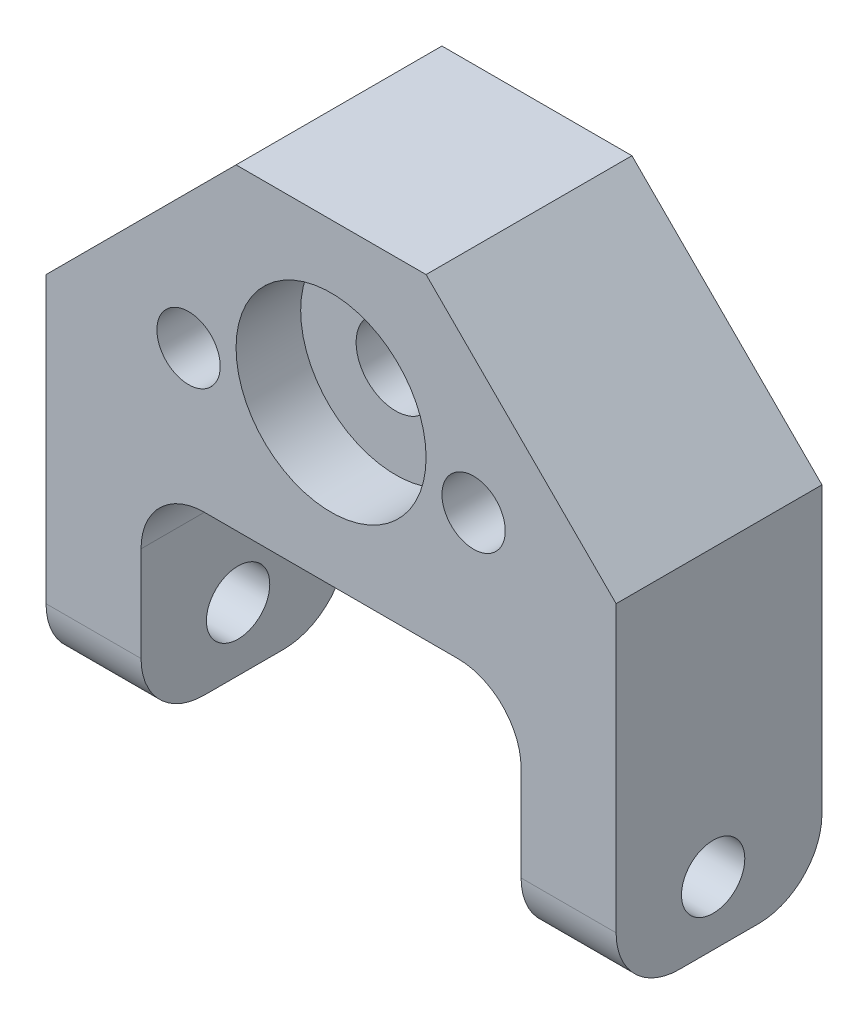
SolidWorks part; units mm, degrees
material "1060 Alloy"
ref_plane "Front" through (0, 0, 0) normal (0, 0, 1) x (1, 0, 0)
ref_plane "Top" through (0, 0, 0) normal (0, 1, 0) x (1, 0, 0)
ref_plane "Right" through (0, 0, 0) normal (1, 0, 0) x (0, 0, -1)
sketch "Sketch1" plane through (0, 0, 0) normal (0, 0, 1) x (1, 0, 0)
  line L1 (28.575, -15.875) -> (-28.575, -15.875)
  line L2 (28.575, -15.875) -> (28.575, 15.875)
  line L3 (28.575, 15.875) -> (-28.575, 15.875)
  line L4 (-28.575, -15.875) -> (-28.575, 15.875)
  line L5 (28.575, -15.875) -> (-28.575, 15.875) construction
  line L6 (28.575, 15.875) -> (-28.575, -15.875) construction
  point P0 (0, 0)
  dimension "D1" = 31.75
  dimension "D2" = 57.15
extrude "Boss-Extrude1" add sketch "Sketch1" along normal blind 20.6375
sketch "Sketch2" plane through (0, 0, 0) normal (0, 0, -1) x (-1, 0, 0)
  circle A0 centre (0, 0) radius 11.1125
  dimension "D1" = 22.225
extrude "Cut-Extrude1" cut sketch "Sketch2" against normal blind 6.985
sketch "Sketch3" plane through (0, 0, 6.985) normal (0, 0, -1) x (-1, 0, 0)
  circle A0 centre (0, 0) radius 8.255
  dimension "D1" = 16.51
extrude "Cut-Extrude2" cut sketch "Sketch3" against normal blind 2.413
sketch "Sketch4" plane through (0, 0, 9.398) normal (0, 0, -1) x (-1, 0, 0)
  circle A0 centre (0, 0) radius 3.9688
  dimension "D1" = 7.9375
extrude "Cut-Extrude3" cut sketch "Sketch4" against normal through all
sketch "Sketch6" plane through (0, 0, 9.398) normal (0, 0, -1) x (-1, 0, 0)
  circle A0 centre (0, 0) radius 9.525
  dimension "D1" = 19.05
extrude "Cut-Extrude4" cut sketch "Sketch6" against normal through all from offset 4.7625 offset against normal yes
sketch "Sketch7" plane through (0, -15.875, 0) normal (0, -1, 0) x (1, 0, 0)
  line L0 (-28.575, 0) -> (28.575, 0) construction
  line L1 (-28.575, 20.6375) -> (-19.05, 20.6375)
  line L2 (-28.575, 20.6375) -> (-28.575, 0)
  line L3 (-28.575, 0) -> (-19.05, 0)
  line L4 (-19.05, 20.6375) -> (-19.05, 0)
  line L6 (28.575, 20.6375) -> (19.05, 20.6375)
  line L7 (28.575, 20.6375) -> (28.575, 0)
  line L8 (28.575, 0) -> (19.05, 0)
  line L9 (19.05, 20.6375) -> (19.05, 0)
  dimension "D1" = 9.525
extrude "Boss-Extrude2" add sketch "Sketch7" along normal blind 22.225
sketch "Sketch9" plane through (28.575, 0, 0) normal (1, 0, 0) x (0, 0, -1)
  line L0 (0, -38.1) -> (-20.6375, -38.1) construction
  circle A0 centre (-10.9095, -31.75) radius 3.175
  dimension "D2" = 6.35
  dimension "D1" = 6.35
extrude "Cut-Extrude5" cut sketch "Sketch9" against normal through all
fillet "Fillet1" radius 6.35 2 edges at (19.05, -15.875, 10.3187) (-19.05, -15.875, 10.3187)
hole_wizard "1/4 (0.2500) Dowel Hole1" positions "Sketch10" profile "Sketch11" hole size "1/4" standard "ANSI Inch"
sketch "Sketch10" plane through (0, 0, 20.6375) normal (0, 0, 1) x (1, 0, 0)
  circle A0 centre (-14.2877, -2.413) radius 3.175 construction
  circle A3 centre (14.2873, -2.4155) radius 3.175 construction
  point P0 (-14.2877, -2.413)
  point P2 (14.2873, -2.4155)
  point P5 (0, 0)
  point P8 (0, 0)
  point P9 (0, 0)
  point P12 (0, 0)
sketch "Sketch11" plane through (-14.2877, -2.413, 20.6375) normal (1, 0, 0) x (0, -1, 0)
  line L0 (0, 0) -> (0, 11.4327)
  line L1 (0, 11.4327) -> (3.175, 9.525)
  line L2 (3.175, 9.525) -> (3.175, 0)
  line L5 (3.175, 0) -> (0, 0)
  line L10 (0, 11.4327) -> (-3.175, 9.525) construction
  line L11 (0, -6.35) -> (0, 107.95) construction
  dimension "Hole Dia." = 6.35
  dimension "Hole Depth" = 9.525
  dimension "Drill Angle" = 118
fillet "Fillet3" radius 6.35 4 edges at (23.8125, -38.1, 0) (23.8125, -38.1, 20.6375) (-23.8125, -38.1, 20.6375) (-23.8125, -38.1, 0)
chamfer "Chamfer1" distance 19.05 angle 45 2 edges at (28.575, 15.875, 10.3187) (-28.575, 15.875, 10.3187)
